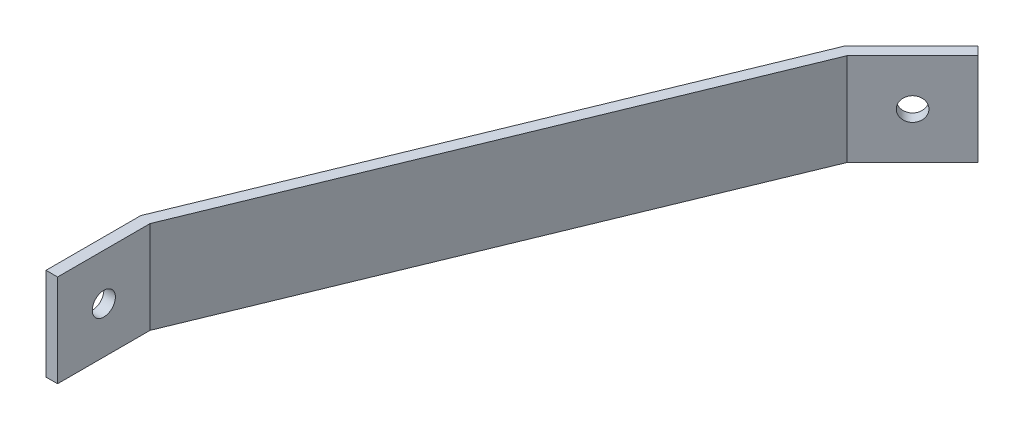
SolidWorks part; units mm, degrees
ref_plane "Front Plane" through (0, 0, 0) normal (0, 0, 1) x (1, 0, 0)
ref_plane "Top Plane" through (0, 0, 0) normal (0, 1, 0) x (1, 0, 0)
ref_plane "Right Plane" through (0, 0, 0) normal (1, 0, 0) x (0, 0, -1)
sketch3d "3DSketch1"
  line L8 (8.6966, 1397.9044, 368.5729) -> (8.6966, 178.7044, 368.5729)
  line L9 (6.5884, 178.7044, 366.4647) -> (6.5884, 1397.9044, 366.4647)
  line L10 (6.5884, 1397.9044, 345.2811) -> (6.5884, 178.7044, 345.2811)
  line L11 (8.6966, 178.7044, 343.1729) -> (8.6966, 1397.9044, 343.1729)
  line L12 (63.8502, 1397.9044, 209.0468) -> (63.8502, 178.7044, 209.0468)
  line L13 (81.8107, 178.7044, 191.0863) -> (81.8107, 1397.9044, 191.0863)
  line L14 (63.8502, 178.7044, 206.0654) -> (63.8502, 1397.9044, 206.0654)
  line L15 (78.8292, 1397.9044, 191.0863) -> (78.8292, 178.7044, 191.0863)
  circle A2 centre (6.5884, 788.3044, 355.8729) radius 3.175
  circle A3 centre (71.3397, 788.3044, 198.5758) radius 3.175
  point P5 (0, 0, 0)
  point P6 (0, 0, 0)
  point P12 (0, 0, 0)
  point P23 (9.7634, 788.3044, 355.8729)
  point P25 (73.5848, 788.3044, 200.8209)
ref_plane "Plane1" through (0, 178.7044, 0) normal (0, 1, 0) x (1, 0, 0)
ref_plane "Plane2" through (0, 788.3044, 0) normal (0, 1, 0) x (1, 0, 0)
sketch "Sketch2" plane through (0, 788.3044, 0) normal (0, 1, 0) x (1, 0, 0)
  line L0 (80.32, -189.5956) -> (62.3595, -207.5561)
  line L1 (81.8107, -191.0863) -> (78.232, -187.5076) construction
  line L2 (63.8502, -209.0468) -> (60.8687, -206.0654) construction
  line L3 (6.5884, -343.1729) -> (6.5884, -368.5729)
  line L4 (8.6966, -343.1729) -> (0, -343.1729) construction
  line L5 (8.6966, -368.5729) -> (-2.3226, -368.5729) construction
  line L6 (62.3595, -207.5561) -> (6.5884, -343.1729)
extrude "Extrude-Thin1" add sketch "Sketch2" along normal mid plane 25.4 thin thin type one direction wall 3.175
sketch "Sketch4" plane through (134.9578, 0, 134.9578) normal (0.7071, 0, 0.7071) x (0.7071, 0, -0.7071)
  circle A0 centre (-89.9695, 788.3044) radius 3.175
  circle A1 centre (-89.9695, 788.3044) radius 3.175 construction
extrude "Cut-Extrude2" cut sketch "Sketch4" against normal through all
extrude "Cut-Extrude3" cut sketch "3DSketch1" along direction (1, 0, 0) on the side against the normal blind 10 contours A2
